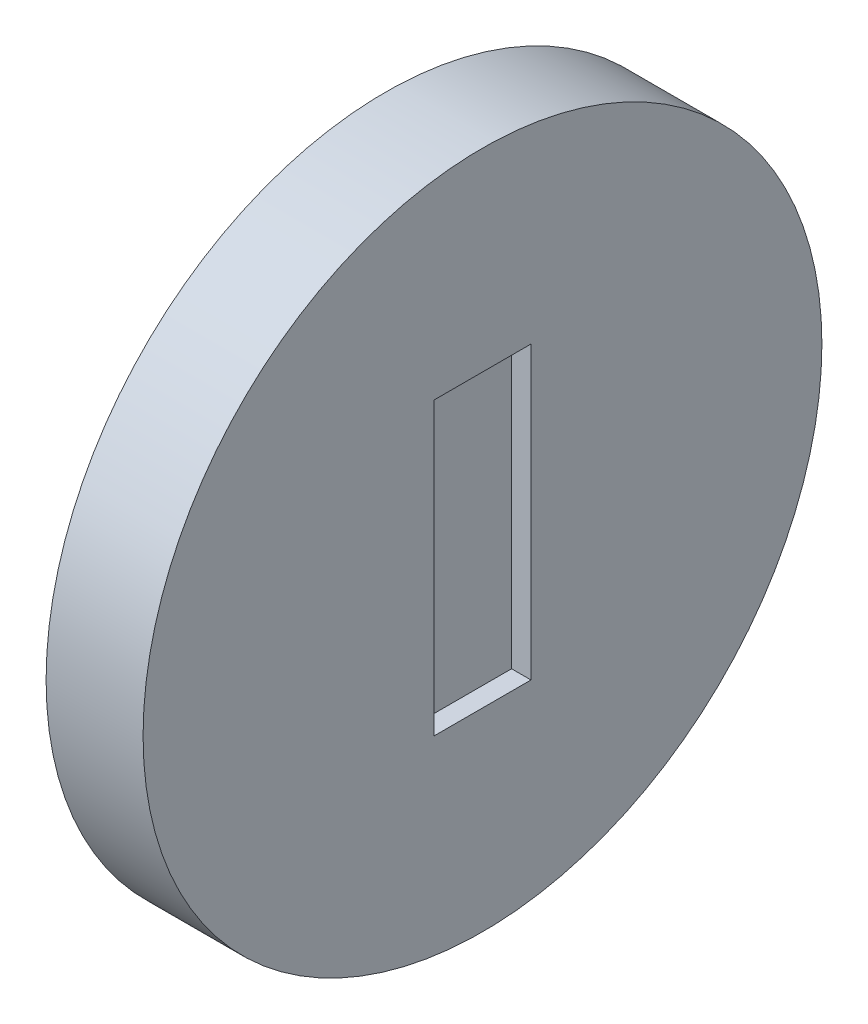
SolidWorks part; units mm, degrees
ref_plane "Front Plane" through (0, 0, 0) normal (0, 0, 1) x (1, 0, 0)
ref_plane "Top Plane" through (0, 0, 0) normal (0, 1, 0) x (1, 0, 0)
ref_plane "Right Plane" through (0, 0, 0) normal (1, 0, 0) x (0, 0, -1)
sketch "Sketch1" plane through (0, 0, 0) normal (1, 0, 0) x (0, 0, -1)
  line L1 (2.5, -7.5) -> (-2.5, -7.5)
  line L2 (2.5, -7.5) -> (2.5, 7.5)
  line L3 (2.5, 7.5) -> (-2.5, 7.5)
  line L4 (-2.5, -7.5) -> (-2.5, 7.5)
  line L5 (2.5, -7.5) -> (-2.5, 7.5) construction
  line L6 (2.5, 7.5) -> (-2.5, -7.5) construction
  circle A0 centre (0, 0) radius 17.5
  dimension "D1" = 35
  dimension "D2" = 5
  dimension "D3" = 15
extrude "Boss-Extrude1" add sketch "Sketch1" against normal blind 5 contours L4 L1 L2 L3 | A0 L1 L4 L3 L2 region at (0, 0, 0) region at (0, 0, 17.005)
extrude "Cut-Extrude1" cut sketch "Sketch1<3>" against normal blind 1 contours L4 L1 L2 L3 region at (0, 0, 0)
sketch "Sketch1<3>" plane through (0, 0, 0) normal (1, 0, 0) x (0, 0, -1) same geometry as "Sketch1"
